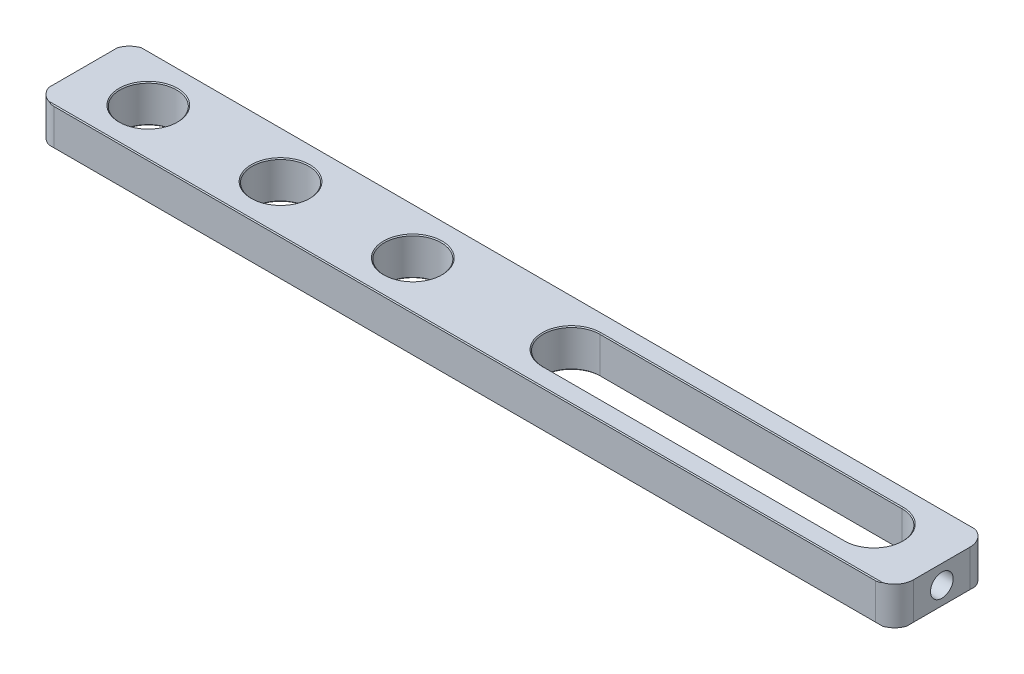
SolidWorks part; units mm, degrees
ref_plane "前视基准面" through (0, 0, 0) normal (0, 0, 1) x (1, 0, 0)
ref_plane "上视基准面" through (0, 0, 0) normal (0, 1, 0) x (1, 0, 0)
ref_plane "右视基准面" through (0, 0, 0) normal (1, 0, 0) x (0, 0, -1)
sketch "草图1" plane through (0, 0, 0) normal (0, 1, 0) x (1, 0, 0)
  line L1 (227.5, -25) -> (-227.5, -25)
  line L2 (227.5, -25) -> (227.5, 25)
  line L3 (227.5, 25) -> (-227.5, 25)
  line L4 (-227.5, -25) -> (-227.5, 25)
  line L5 (227.5, -25) -> (-227.5, 25) construction
  line L6 (227.5, 25) -> (-227.5, -25) construction
  point P0 (0, 0)
  dimension "D1" = 455
  dimension "D2" = 50
extrude "凸台-拉伸1" add sketch "草图1" along normal blind 20
sketch "草图2" plane through (0, 20, 0) normal (0, 1, 0) x (1, 0, 0)
  line L0 (31.5, 0) -> (191.5, 0) construction
  line L1 (31.5, 15) -> (191.5, 15)
  line L2 (31.5, -15) -> (191.5, -15)
  line L3 (-227.5, 25) -> (-227.5, -25) construction
  line L4 (-227.5, 0) -> (227.5, 0) construction
  line L5 (227.5, -25) -> (227.5, 25) construction
  circle A0 centre (-192.5, 0) radius 15
  circle A1 centre (-122.5, 0) radius 15
  circle A2 centre (-52.5, 0) radius 15
  arc A3 (31.5, 15) -> (31.5, -15) centre (31.5, 0) ccw
  arc A4 (191.5, -15) -> (191.5, 15) centre (191.5, 0) ccw
  point P8 (111.5, 0)
  point P13 (0, 0)
  point P16 (0, 0)
  dimension "D1" = 30
  dimension "D2" = 35
  dimension "D3" = 70
  dimension "D4" = 70
  dimension "D5" = 160
  dimension "D6" = 30
  dimension "D7" = 69
extrude "切除-拉伸1" cut sketch "草图2" against normal through all
sketch "草图3" plane through (227.5, 0, 0) normal (1, 0, 0) x (0, 0, -1)
  line L0 (-25, 20) -> (-25, 0) construction
  line L1 (-25, 20) -> (25, 20) construction
  circle A0 centre (0, 10) radius 6
  point P2 (0, 0)
  point P5 (-25, 10)
  point P6 (0, 0)
  point P9 (0, 20)
  dimension "D1" = 12
extrude "切除-拉伸2" cut sketch "草图3" against normal up to next
chamfer "倒角1" distance 0.5 14 edges at (111.5, 0, 15) (206.5, 0, 0) (16.5, 0, 0) (111.5, 0, -15) (111.5, 20, 15) (206.5, 20, 0) (16.5, 20, 0) (111.5, 20, -15) (-52.5, 0, 15) (-52.5, 20, 15) (-122.5, 0, 15) (-122.5, 20, 15) (-192.5, 0, 15) (-192.5, 20, 15)
chamfer "倒角2" distance 0.5 7 edges at (227.5, 0, 0) (0, 0, -25) (-227.5, 0, 0) (0, 0, 25) (0, 20, 25) (-227.5, 20, 0) (0, 20, -25)
fillet "圆角1" radius 10 4 edges at (227.5, 10, 25) (227.5, 10, -25) (-227.5, 10, -25) (-227.5, 10, 25)
